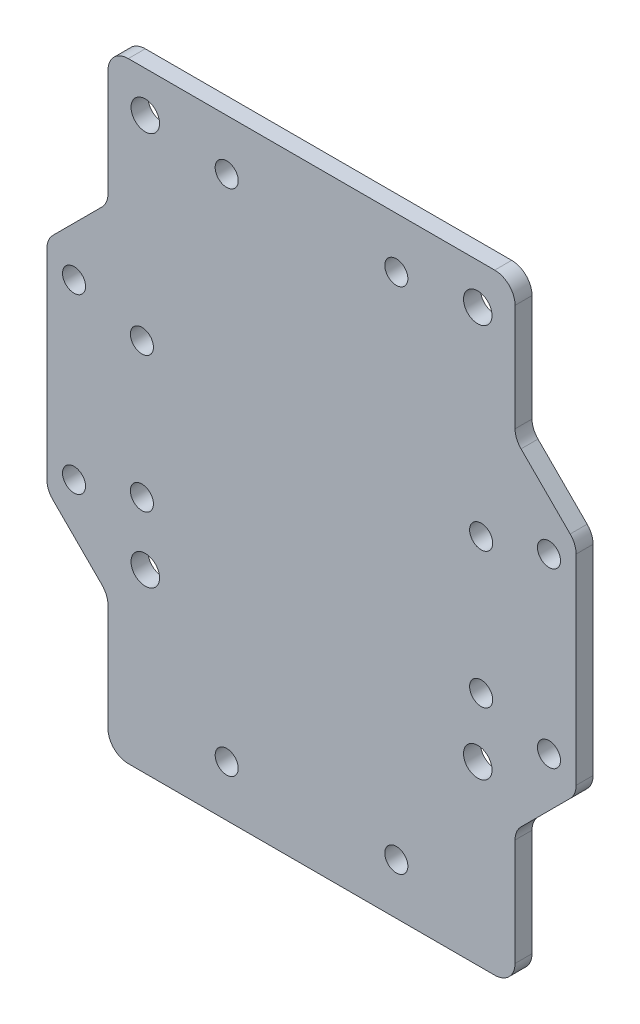
SolidWorks part; units mm, degrees
material "Thornel Mat VMA"
ref_plane "Front Plane" through (0, 0, 0) normal (0, 0, 1) x (1, 0, 0)
ref_plane "Top Plane" through (0, 0, 0) normal (0, 1, 0) x (1, 0, 0)
ref_plane "Right Plane" through (0, 0, 0) normal (1, 0, 0) x (0, 0, -1)
sketch "Sketch1" plane through (0, 0, 0) normal (0, 0, 1) x (1, 0, 0)
  line L0 (-39, -16) -> (-39, 16)
  line L5 (-30, 45) -> (30, 45)
  line L6 (-30, 45) -> (-30, -45)
  line L12 (-30, -45) -> (30, -45)
  line L17 (30, 45) -> (30, -45)
  line L19 (-30, 45) -> (30, -45) construction
  line L20 (-30, -45) -> (30, 45) construction
  line L21 (-39, 0) -> (39, 0) construction
  line L22 (-39, 16) -> (-30, 25)
  line L23 (-39, -16) -> (-30, -25)
  line L24 (0, 0) -> (0, 25) construction
  line L25 (39, -16) -> (30, -25)
  line L26 (39, 16) -> (30, 25)
  line L27 (39, -16) -> (39, 16)
  point P0 (0, 0)
  dimension "D1" = 60
  dimension "D2" = 90
  dimension "D3" = 9
  dimension "D4" = 16
  dimension "D5" = 135
extrude "Boss-Extrude1" add sketch "Sketch1" along normal mid plane 2.5 contours L5 | L17 L5 L6 L12 | L0 L23 L6 L22 | L25 L27 L26 L17 region at (-34.1707, 0, 0) region at (0, 0, 0) region at (34.1707, 0, 0)
fillet "Fillet1" radius 3 12 edges at (30, 45, 0) (30, -45, 0) (-30, -45, 0) (-30, 45, 0) (30, 25, 0) (39, 16, 0) (39, -16, 0) (30, -25, 0) (-30, -25, 0) (-39, -16, 0) (-39, 16, 0) (-30, 25, 0)
hole_wizard "Ø4.2 (4.2) Diameter Hole1" positions "Sketch2" profile "Sketch3" hole size "Ø4.2" standard "ANSI Metric" end condition through all
sketch "Sketch2" plane through (0, 0, -1.25) normal (0, 0, -1) x (-1, 0, 0)
  point P0 (-24.5, -19)
  point P3 (24.5, -19)
  point P6 (24.5, 39)
  point P9 (-24.5, 39)
sketch "Sketch3" plane through (24.5, -19, -1.25) normal (1, 0, 0) x (0, 1, 0)
  line L0 (0, 0) -> (0, 2.5)
  line L1 (0, 2.5) -> (2.1, 2.5)
  line L2 (2.1, 2.5) -> (2.1, 0)
  line L5 (2.1, 0) -> (0, 0)
  line L11 (0, -6.35) -> (0, 107.95) construction
  dimension "Thru Hole Dia." = 4.2
  dimension "Thru Hole Depth" = 2.5
hole_wizard "M3 Clearance Hole1" positions "Sketch4" profile "Sketch5" hole size "M3" standard "ANSI Metric" end condition through all
sketch "Sketch4" plane through (0, 0, -1.25) normal (0, 0, -1) x (-1, 0, 0)
  point P0 (-35, 12.75)
  point P3 (-35, -12.75)
  point P6 (35, -12.75)
  point P9 (35, 12.75)
sketch "Sketch5" plane through (35, 12.75, -1.25) normal (1, 0, 0) x (0, 1, 0)
  line L0 (0, 0) -> (0, 2.5)
  line L1 (0, 2.5) -> (1.7, 2.5)
  line L2 (1.7, 2.5) -> (1.7, 0)
  line L5 (1.7, 0) -> (0, 0)
  line L11 (0, -6.35) -> (0, 107.95) construction
  dimension "Thru Hole Dia." = 3.4
  dimension "Thru Hole Depth" = 2.5
hole_wizard "M3 Clearance Hole2" positions "Sketch6" profile "Sketch7" hole size "M3" standard "ANSI Metric" end condition through all
sketch "Sketch6" plane through (0, 0, 1.25) normal (0, 0, 1) x (1, 0, 0)
  point P0 (-12.5, -37.5)
  point P3 (12.5, -37.5)
  point P6 (-12.5, 37.5)
  point P9 (12.5, 37.5)
  point P12 (-25, 10)
  point P15 (-25, -10)
  point P18 (25, -10)
  point P21 (25, 10)
sketch "Sketch7" plane through (-12.5, -37.5, 1.25) normal (1, 0, 0) x (0, -1, 0)
  line L0 (0, 0) -> (0, 2.5)
  line L1 (0, 2.5) -> (1.7, 2.5)
  line L2 (1.7, 2.5) -> (1.7, 0)
  line L5 (1.7, 0) -> (0, 0)
  line L11 (0, -6.35) -> (0, 107.95) construction
  dimension "Thru Hole Dia." = 3.4
  dimension "Thru Hole Depth" = 2.5
